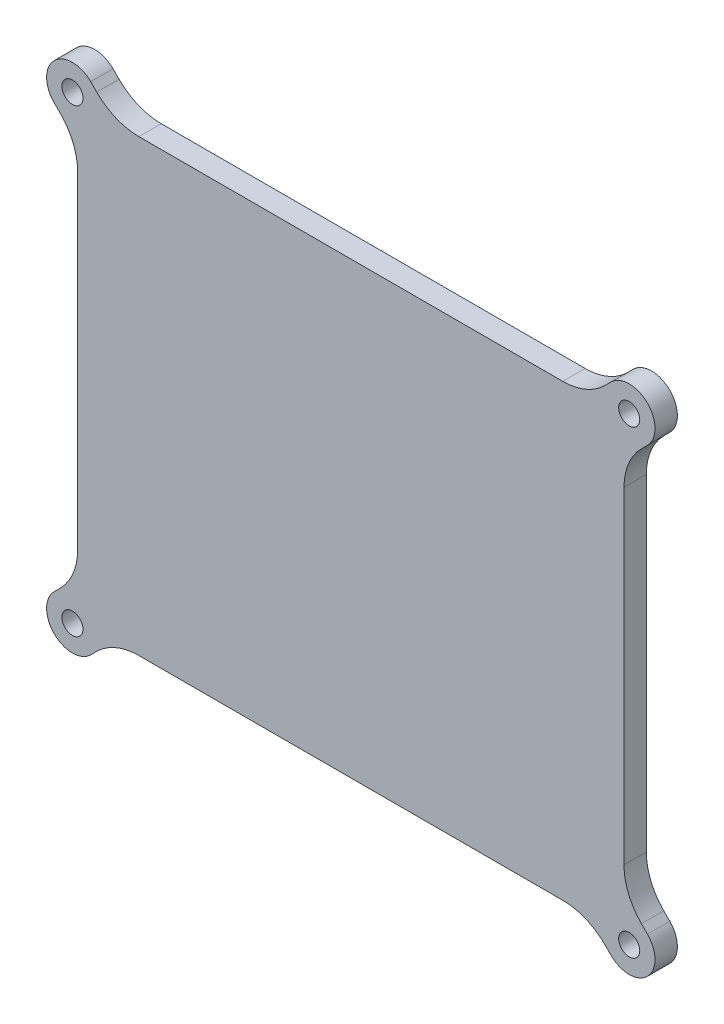
SolidWorks part; units mm, degrees
material "Acrylic (Medium-high impact)"
ref_plane "X-Y Datum" through (0, 0, 0) normal (0, 0, 1) x (1, 0, 0)
ref_plane "X-Z Datum" through (0, 0, 0) normal (0, 1, 0) x (1, 0, 0)
ref_plane "Y-Z Datum" through (0, 0, 0) normal (1, 0, 0) x (0, 0, -1)
sketch "Sketch2" plane through (0, 0, 0) normal (0, 0, 1) x (1, 0, 0)
  line L14 (-63.3851, 38.2341) -> (-62.1032, 36.9523)
  line L15 (-58.3835, 27.9721) -> (-58.3835, -41.6756)
  line L24 (-62.1032, -50.6558) -> (-63.3851, -51.9376)
  line L33 (-55.6069, -59.7158) -> (-54.3251, -58.434)
  line L34 (-45.3448, -54.7143) -> (44.9403, -54.7143)
  line L35 (53.9206, -58.434) -> (55.2024, -59.7158)
  line L36 (62.9806, -51.9376) -> (61.6987, -50.6558)
  line L37 (57.979, -41.6756) -> (57.979, 27.9721)
  line L38 (61.6987, 36.9523) -> (62.9806, 38.2341)
  line L39 (55.2024, 46.0123) -> (53.9206, 44.7305)
  line L40 (44.9403, 41.0107) -> (-45.3448, 41.0107)
  line L41 (-54.3251, 44.7305) -> (-55.6069, 46.0123)
  line L42 (-63.3851, 38.2341) -> (-62.1032, 36.9523)
  line L43 (-58.3835, 27.9721) -> (-58.3835, -41.6756)
  line L44 (-62.1032, -50.6558) -> (-63.3851, -51.9376)
  line L45 (-55.6069, -59.7158) -> (-54.3251, -58.434)
  line L46 (-45.3448, -54.7143) -> (44.9403, -54.7143)
  line L47 (53.9206, -58.434) -> (55.2024, -59.7158)
  line L48 (62.9806, -51.9376) -> (61.6987, -50.6558)
  line L49 (57.979, -41.6756) -> (57.979, 27.9721)
  line L50 (61.6987, 36.9523) -> (62.9806, 38.2341)
  line L51 (55.2024, 46.0123) -> (53.9206, 44.7305)
  line L52 (44.9403, 41.0107) -> (-45.3448, 41.0107)
  line L53 (-54.3251, 44.7305) -> (-55.6069, 46.0123)
  arc A52 (-58.3835, 27.9721) -> (-62.1032, 36.9523) centre (-71.0835, 27.9721) ccw
  arc A53 (-62.1032, -50.6558) -> (-58.3835, -41.6756) centre (-71.0835, -41.6756) ccw
  arc A54 (-63.3851, -51.9376) -> (-55.6069, -59.7158) centre (-59.496, -55.8267) ccw
  arc A55 (-45.3448, -54.7143) -> (-54.3251, -58.434) centre (-45.3448, -67.4143) ccw
  arc A56 (53.9206, -58.434) -> (44.9403, -54.7143) centre (44.9403, -67.4143) ccw
  arc A57 (55.2024, -59.7158) -> (62.9806, -51.9376) centre (59.0915, -55.8267) ccw
  arc A58 (57.979, -41.6756) -> (61.6987, -50.6558) centre (70.679, -41.6756) ccw
  arc A59 (61.6987, 36.9523) -> (57.979, 27.9721) centre (70.679, 27.9721) ccw
  arc A60 (62.9806, 38.2341) -> (55.2024, 46.0123) centre (59.0915, 42.1232) ccw
  arc A61 (44.9403, 41.0107) -> (53.9206, 44.7305) centre (44.9403, 53.7107) ccw
  arc A62 (-54.3251, 44.7305) -> (-45.3448, 41.0107) centre (-45.3448, 53.7107) ccw
  arc A63 (-55.6069, 46.0123) -> (-63.3851, 38.2341) centre (-59.496, 42.1232) ccw
  arc A64 (-58.3835, 27.9721) -> (-62.1032, 36.9523) centre (-71.0835, 27.9721) ccw
  arc A65 (-62.1032, -50.6558) -> (-58.3835, -41.6756) centre (-71.0835, -41.6756) ccw
  arc A66 (-63.3851, -51.9376) -> (-55.6069, -59.7158) centre (-59.496, -55.8267) ccw
  arc A67 (-45.3448, -54.7143) -> (-54.3251, -58.434) centre (-45.3448, -67.4143) ccw
  arc A68 (53.9206, -58.434) -> (44.9403, -54.7143) centre (44.9403, -67.4143) ccw
  arc A69 (55.2024, -59.7158) -> (62.9806, -51.9376) centre (59.0915, -55.8267) ccw
  arc A70 (57.979, -41.6756) -> (61.6987, -50.6558) centre (70.679, -41.6756) ccw
  arc A71 (61.6987, 36.9523) -> (57.979, 27.9721) centre (70.679, 27.9721) ccw
  arc A72 (62.9806, 38.2341) -> (55.2024, 46.0123) centre (59.0915, 42.1232) ccw
  arc A73 (44.9403, 41.0107) -> (53.9206, 44.7305) centre (44.9403, 53.7107) ccw
  arc A74 (-54.3251, 44.7305) -> (-45.3448, 41.0107) centre (-45.3448, 53.7107) ccw
  arc A75 (-55.6069, 46.0123) -> (-63.3851, 38.2341) centre (-59.496, 42.1232) ccw
  dimension "D1" = 0
extrude "Boss-Extrude1" add sketch "Sketch2" along normal blind 4.7625
hole_wizard "M4 Clearance Hole1" positions "Sketch5" profile "Sketch4" hole size "M4" standard "ANSI Metric" end condition through all
sketch "Sketch5" plane through (0, 0, 4.7625) normal (0, 0, 1) x (1, 0, 0)
  point P0 (-59.496, -55.8267)
  point P3 (-59.496, 42.1232)
  point P6 (59.0915, 42.1232)
  point P9 (59.0915, -55.8267)
sketch "Sketch4" plane through (-59.496, -55.8267, 4.7625) normal (1, 0, 0) x (0, -1, 0)
  line L0 (0, 0) -> (0, 4.7625)
  line L1 (0, 4.7625) -> (2.25, 4.7625)
  line L2 (2.25, 4.7625) -> (2.25, 0)
  line L5 (2.25, 0) -> (0, 0)
  line L11 (0, -6.35) -> (0, 107.95) construction
  dimension "Thru Hole Dia." = 4.5
  dimension "Thru Hole Depth" = 4.7625
